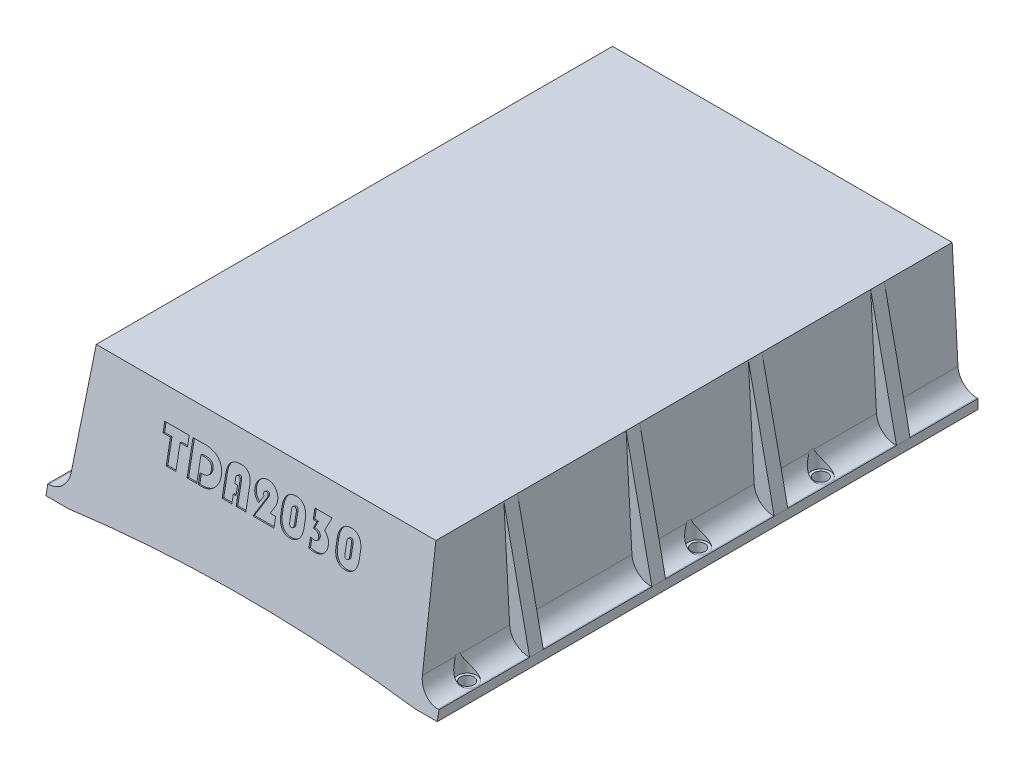
SolidWorks part; units mm, degrees
ref_plane "前视基准面" through (0, 0, 0) normal (0, 0, 1) x (1, 0, 0)
ref_plane "上视基准面" through (0, 0, 0) normal (0, 1, 0) x (1, 0, 0)
ref_plane "右视基准面" through (0, 0, 0) normal (1, 0, 0) x (0, 0, -1)
sketch "草图1" plane through (0, 0, 0) normal (0, 0, 1) x (1, 0, 0)
  line L0 (-63.6921, 0) -> (63.6921, 0) construction
  line L1 (-65, 3.5) -> (-62.5, 48.5)
  line L2 (-72, 0) -> (-63.6921, 0)
  line L3 (-72, 0) -> (-72, 3.5)
  line L4 (-72, 3.5) -> (-65, 3.5)
  line L6 (72, 0) -> (63.6921, 0)
  line L7 (72, 0) -> (72, 3.5)
  line L8 (72, 3.5) -> (65, 3.5)
  line L10 (-62.5, 48.5) -> (62.5, 48.5)
  line L11 (62.5, 48.5) -> (65, 3.5)
  line L12 (-63.6921, 0) -> (-61.081, 47)
  line L13 (-61.081, 47) -> (61.081, 47)
  line L14 (61.081, 47) -> (63.6921, 0)
  line L15 (61.081, 47) -> (63.5023, 3.4168) construction
  line L16 (-63.5023, 3.4168) -> (-61.081, 47) construction
  point P2 (0, 48.5)
  point P3 (0, 0)
  dimension "D1" = 7
  dimension "D2" = 3.5
  dimension "D3" = 144
  dimension "D4" = 47
  dimension "D5" = 125
  dimension "D6" = 1.5
extrude "凸台-拉伸1" add sketch "草图1" along normal blind 195
sketch "草图2" plane through (0, 0, 0) normal (0, -1, 0) x (1, 0, 0)
  line L0 (-61.081, 195) -> (61.081, 195) construction
  line L1 (-68, 182) -> (68, 182) construction
  line L2 (-68, 182) -> (-68, 51.849) construction
  line L3 (-68, 51.849) -> (68, 51.849) construction
  line L4 (68, 182) -> (68, 51.849) construction
  line L5 (68, 97) -> (-68, 97) construction
  circle A0 centre (68, 51.849) radius 2.5
  circle A1 centre (-68, 51.849) radius 2.5
  circle A2 centre (-68, 182) radius 2.5
  circle A3 centre (68, 182) radius 2.5
  circle A4 centre (68, 97) radius 2.5
  circle A5 centre (-68, 97) radius 2.5
  point P4 (0, 51.849)
  dimension "D4" = 5
  dimension "D1" = 136
  dimension "D2" = 130.151
  dimension "D3" = 13
  dimension "D5" = 85
sketch "草图3" plane through (72, 0, 0) normal (1, 0, 0) x (0, 0, -1)
  line L0 (-195, 48.5) -> (-186, 48.5)
  line L1 (-195, 48.5) -> (0, 48.5) construction
  line L2 (-186, 48.5) -> (-195, 0)
  line L3 (-195, 0) -> (-195, 48.5)
  dimension "D1" = 9
extrude "切除-拉伸1" cut sketch "草图3" against normal through all
sketch "草图7" plane through (72, 0, 0) normal (1, 0, 0) x (0, 0, -1)
  line L0 (-186, 48.5) -> (-188, 48.5)
  line L1 (-188, 48.5) -> (-197, 0)
  line L2 (-197, 0) -> (-195, 0)
  line L3 (-195, 0) -> (-186, 48.5)
  dimension "D1" = 2
extrude "凸台-拉伸5" add sketch "草图7" against normal through all
sketch "草图8" plane through (0, 0, 0) normal (0, 0, -1) x (-1, 0, 0)
  line L0 (-62.5, 48.5) -> (-72, 48.5) construction
  line L1 (-65, 3.5) -> (-62.5, 48.5) construction
  line L2 (-65, 3.5) -> (-72, 3.5) construction
  line L3 (-72, 3.5) -> (-72, 48.5) construction
  line L4 (65, 3.5) -> (72, 3.5) construction
  line L5 (62.5, 48.5) -> (65, 3.5) construction
  line L6 (72, 3.5) -> (72, 48.5) construction
  line L7 (72, 48.5) -> (62.5, 48.5) construction
  line L8 (65, 3.5) -> (72, 3.5)
  line L9 (62.5, 48.5) -> (65, 3.5)
  line L10 (72, 3.5) -> (72, 48.5)
  line L11 (72, 48.5) -> (62.5, 48.5)
  line L12 (-65, 3.5) -> (-72, 3.5)
  line L13 (-72, 3.5) -> (-72, 48.5)
  line L14 (-65, 3.5) -> (-62.5, 48.5)
  line L15 (-62.5, 48.5) -> (-72, 48.5)
  line L16 (-63.6921, 0) -> (63.6921, 0)
  arc A0 (-63.6921, 0) -> (63.6921, 0) centre (0, -557.3316) cw
extrude "切除-拉伸2" cut sketch "草图8" against normal through all
extrude "切除-拉伸3" cut sketch "草图2" against normal up to next
sketch "草图9" plane through (0, 0, 0) normal (0, 0, -1) x (-1, 0, 0)
  line L0 (72, 0) -> (63.6921, 0) construction
  line L1 (-63.6921, 0) -> (-72, 0) construction
  line L2 (-72, 0) -> (-72, 3.5) construction
  line L3 (72, 3.5) -> (72, 0) construction
  line L4 (65, 3.5) -> (72, 3.5) construction
  line L5 (62.5, 48.5) -> (65, 3.5) construction
  line L6 (-72, 3.5) -> (-65, 3.5) construction
  line L7 (-65, 3.5) -> (-62.5, 48.5) construction
  line L8 (-62.5, 48.5) -> (62.5, 48.5) construction
  line L9 (72, 0) -> (63.6921, 0)
  line L10 (-63.6921, 0) -> (-72, 0)
  line L11 (-72, 0) -> (-72, 3.5)
  line L12 (72, 3.5) -> (72, 0)
  line L13 (65, 3.5) -> (72, 3.5)
  line L14 (62.5, 48.5) -> (65, 3.5)
  line L15 (-72, 3.5) -> (-65, 3.5)
  line L16 (-65, 3.5) -> (-62.5, 48.5)
  line L17 (-62.5, 48.5) -> (62.5, 48.5)
  arc A0 (63.6921, 0) -> (-63.6921, 0) centre (0, -557.3316) ccw construction
  arc A1 (63.6921, 0) -> (-63.6921, 0) centre (0, -557.3316) ccw
extrude "凸台-拉伸6" add sketch "草图9" along normal blind 2
sketch "草图10" plane through (0, 0, -2) normal (0, 0, -1) x (-1, 0, 0)
  line L0 (-6, 10) -> (6, 10) construction
  line L1 (-6, 12.6) -> (6, 12.6)
  line L2 (-6, 7.4) -> (6, 7.4)
  arc A0 (-6, 12.6) -> (-6, 7.4) centre (-6, 10) ccw
  arc A1 (6, 7.4) -> (6, 12.6) centre (6, 10) ccw
  point P2 (0, 10)
  point P7 (0, 0)
  dimension "D1" = 2.6
  dimension "D2" = 12
  dimension "D3" = 10
extrude "切除-拉伸4" cut sketch "草图10" against normal up to next
sketch "草图11" plane through (0, 35.3398, 190.4421) normal (0, 0.1825, 0.9832) x (1, 0, 0)
  text T0 "TDA2030" font "华文琥珀" height 12
extrude "切除-拉伸5" cut sketch "草图11" against normal blind 0.6
ref_plane "基准面1" through (0, 0, 23) normal (0, 0, -1) x (-1, 0, 0)
sketch "草图12" plane through (0, 0, 23) normal (0, 0, -1) x (-1, 0, 0)
  line L0 (72, 3.5) -> (65, 3.5) construction
  line L1 (65, 3.5) -> (62.5, 48.5) construction
  line L2 (-65, 3.5) -> (-72, 3.5) construction
  line L3 (-62.5, 48.5) -> (-65, 3.5) construction
  line L4 (72, 3.5) -> (65, 3.5)
  line L5 (65, 3.5) -> (62.5, 48.5)
  line L6 (-65, 3.5) -> (-72, 3.5)
  line L7 (-62.5, 48.5) -> (-65, 3.5)
  line L8 (-62.5, 48.5) -> (-72, 3.5)
  line L10 (62.5, 48.5) -> (72, 3.5)
extrude "凸台-拉伸7" add sketch "草图12" against normal blind 5
ref_plane "基准面2" through (0, 0, 68) normal (0, 0, 1) x (1, 0, 0)
sketch "草图13" plane through (0, 0, 68) normal (0, 0, 1) x (1, 0, 0)
  line L0 (-65, 3.5) -> (-72, 3.5) construction
  line L1 (-72, 3.5) -> (-62.5, 48.5) construction
  line L2 (-62.5, 48.5) -> (-65, 3.5) construction
  line L3 (72, 3.5) -> (65, 3.5) construction
  line L4 (62.5, 48.5) -> (65, 3.5) construction
  line L5 (62.5, 48.5) -> (72, 3.5) construction
  line L6 (-65, 3.5) -> (-72, 3.5)
  line L7 (-72, 3.5) -> (-62.5, 48.5)
  line L8 (-62.5, 48.5) -> (-65, 3.5)
  line L9 (72, 3.5) -> (65, 3.5)
  line L10 (62.5, 48.5) -> (65, 3.5)
  line L11 (62.5, 48.5) -> (72, 3.5)
extrude "凸台-拉伸8" add sketch "草图13" along normal blind 5
ref_plane "基准面3" through (0, 0, 113) normal (0, 0, 1) x (1, 0, 0)
sketch "草图15" plane through (0, 0, 113) normal (0, 0, 1) x (1, 0, 0)
  line L0 (-65, 3.5) -> (-72, 3.5) construction
  line L1 (-72, 3.5) -> (-62.5, 48.5) construction
  line L2 (-62.5, 48.5) -> (-65, 3.5) construction
  line L3 (65, 3.5) -> (72, 3.5) construction
  line L4 (62.5, 48.5) -> (65, 3.5) construction
  line L5 (62.5, 48.5) -> (72, 3.5) construction
  line L6 (-65, 3.5) -> (-72, 3.5)
  line L7 (-72, 3.5) -> (-62.5, 48.5)
  line L8 (-62.5, 48.5) -> (-65, 3.5)
  line L9 (65, 3.5) -> (72, 3.5)
  line L10 (62.5, 48.5) -> (65, 3.5)
  line L11 (62.5, 48.5) -> (72, 3.5)
extrude "凸台-拉伸9" add sketch "草图15" along normal blind 5
ref_plane "基准面4" through (0, 0, 158) normal (0, 0, 1) x (1, 0, 0)
sketch "草图16" plane through (0, 0, 158) normal (0, 0, 1) x (1, 0, 0)
  line L0 (-72, 3.5) -> (-62.5, 48.5) construction
  line L1 (-65, 3.5) -> (-62.5, 48.5) construction
  line L2 (-65, 3.5) -> (-72, 3.5) construction
  line L3 (65, 3.5) -> (72, 3.5) construction
  line L4 (65, 3.5) -> (62.5, 48.5) construction
  line L5 (62.5, 48.5) -> (72, 3.5) construction
  line L6 (-72, 3.5) -> (-62.5, 48.5)
  line L7 (-65, 3.5) -> (-62.5, 48.5)
  line L8 (-65, 3.5) -> (-72, 3.5)
  line L9 (65, 3.5) -> (72, 3.5)
  line L10 (65, 3.5) -> (62.5, 48.5)
  line L11 (62.5, 48.5) -> (72, 3.5)
extrude "凸台-拉伸10" add sketch "草图16" along normal blind 5
fillet "圆角1" radius 7 6 edges at (65, 3.5, 179.6753) (-65, 3.5, 138) (-65, 3.5, 10.5) (-65, 3.5, 48) (-65, 3.5, 93) (-65, 3.5, 179.6753)
sketch "草图17" plane through (0, 3.5, 0) normal (0, 1, 0) x (1, 0, 0)
  circle A0 centre (-68, -51.849) radius 3.5
  circle A1 centre (-68, -97) radius 3.5
  circle A2 centre (-68, -182) radius 3.5
  circle A3 centre (68, -182) radius 3.5
  circle A4 centre (68, -97) radius 3.5
  circle A5 centre (68, -51.849) radius 3.5
  dimension "D1" = 7
extrude "切除-拉伸6" cut sketch "草图17" along normal blind 7
fillet "圆角2" radius 1.6 4 edges at (-62.3866, 23.5, 190.6392) (62.3866, 23.5, 0) (-62.3866, 23.5, 0) (62.3866, 23.5, 190.6392)
